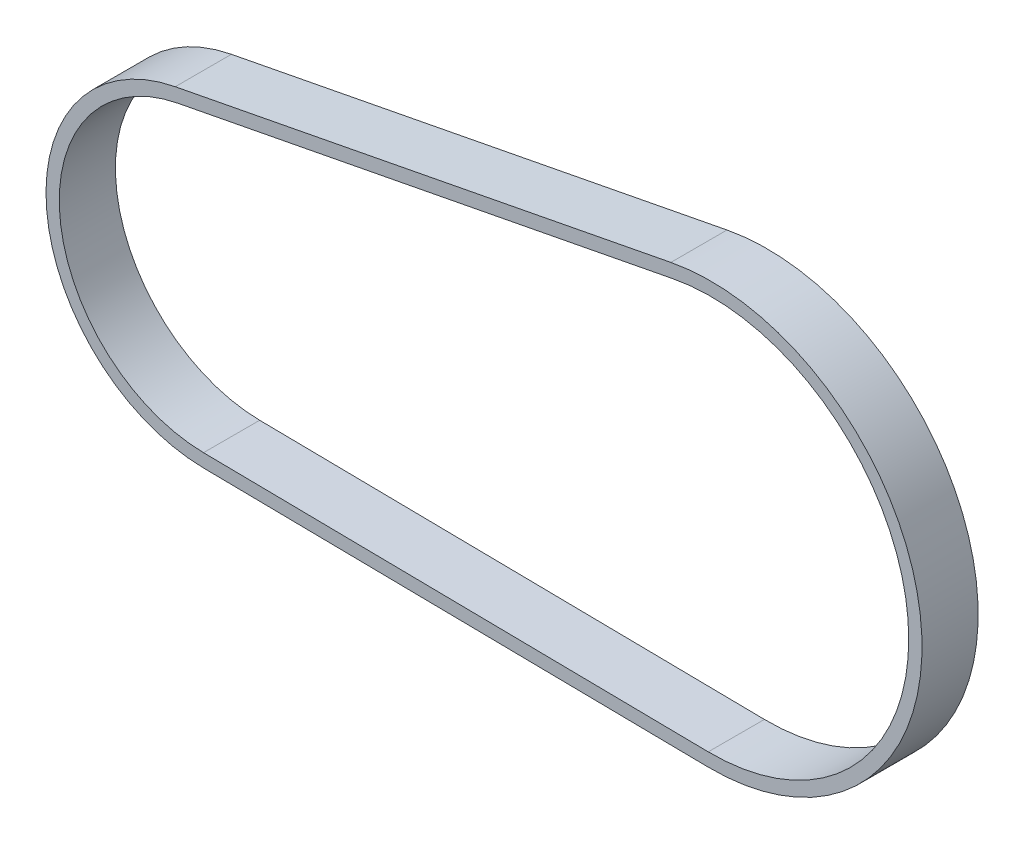
SolidWorks part; units mm, degrees
ref_plane "Front Plane" through (0, 0, 0) normal (0, 0, 1) x (1, 0, 0)
ref_plane "Top Plane" through (0, 0, 0) normal (0, 1, 0) x (1, 0, 0)
ref_plane "Right Plane" through (0, 0, 0) normal (1, 0, 0) x (0, 0, -1)
sketch "Sketch2" plane through (0, 0, 0) normal (0, 0, 1) x (1, 0, 0)
  line L0 (0, 0) -> (1, 0) construction
  line L1 (0, 0) -> (0, 1) construction
  line L4 (56.8315, -18.7939) -> (-0.2406, -18.0324)
  line L5 (-3.4175, 17.7072) -> (52.6255, 28.5234)
  arc A2 (52.6255, 28.5234) -> (56.8315, -18.7939) centre (57.15, 5.08) cw
  arc A3 (-0.2406, -18.0324) -> (-3.4175, 17.7072) centre (0, 0) cw
extrude "Extrude-Thin1" add sketch "Sketch2" against normal mid plane 6.35 thin thin type one direction reverse wall 1.5
